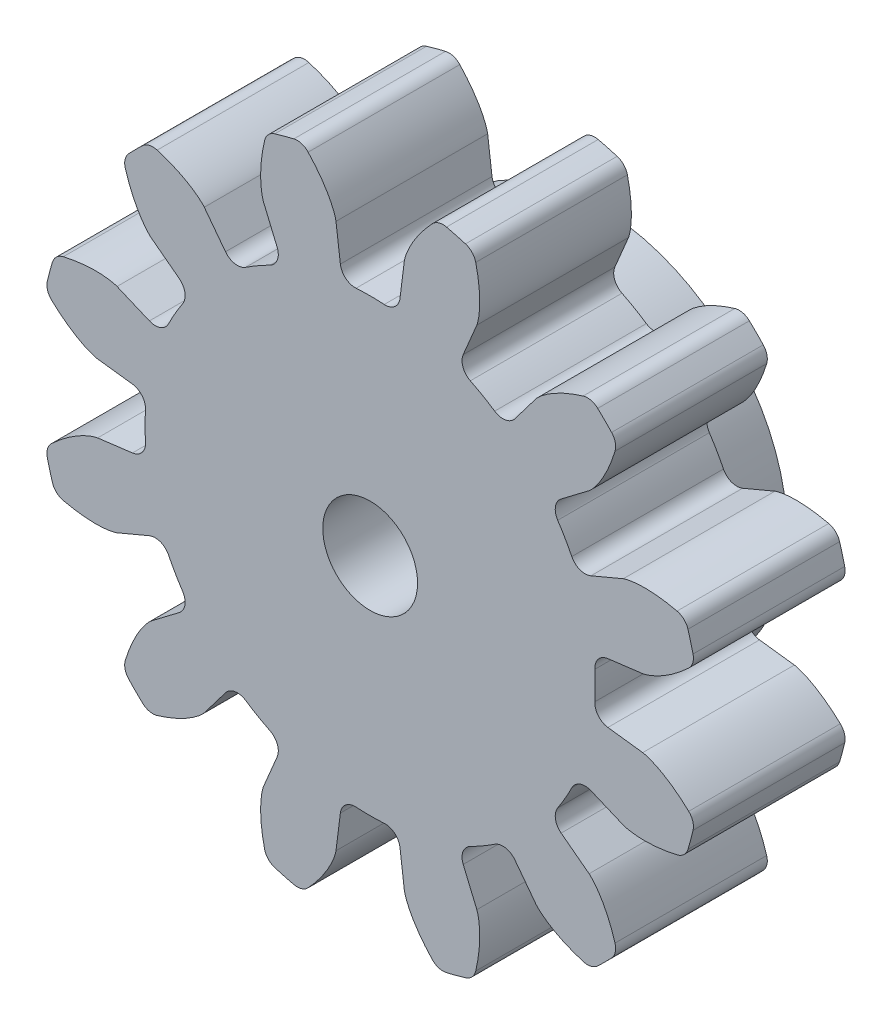
SolidWorks part; units mm, degrees
material "Brass"
ref_plane "Front Plane" through (0, 0, 0) normal (0, 0, 1) x (1, 0, 0)
ref_plane "Top Plane" through (0, 0, 0) normal (0, 1, 0) x (1, 0, 0)
ref_plane "Right Plane" through (0, 0, 0) normal (1, 0, 0) x (0, 0, -1)
sketch "Sketch1" plane through (0, 0, 0) normal (0, 0, 1) x (1, 0, 0)
  circle A0 centre (0, 0) radius 8.75
  dimension "D1" = 17.5
extrude "Boss-Extrude1" add sketch "Sketch1" along normal blind 4
sketch "Sketch2" plane through (0, 0, 4) normal (0, 0, 1) x (1, 0, 0)
  line L0 (7.1881, 0.9014) -> (0, 0) construction
  line L1 (0, 0) -> (7.1881, -0.9014) construction
  line L2 (5.8914, 0.7388) -> (7.1881, 0.9014)
  line L3 (5.8914, -0.7388) -> (7.1881, -0.9014)
  circle A0 centre (0, 0) radius 8.75 construction
  circle A1 centre (0, 0) radius 7.2444 construction
  circle A2 centre (0, 0) radius 7.5 construction
  circle A3 centre (0, 0) radius 5.9375 construction
  arc A4 (8.5637, 1.7962) -> (8.5637, -1.7962) centre (3.6281, 0) cw
  arc A5 (5.8914, -0.7388) -> (5.8914, 0.7388) centre (0, 0) ccw
  spline S0 degree 4 poles (7.1881, 0.9014) (7.1906, 0.9017) (7.1974, 0.9028) (7.2102, 0.9052) (7.231, 0.9098) (7.2574, 0.9165) (7.2912, 0.9262) (7.3308, 0.939) (7.374, 0.9543) (7.4206, 0.9724) (7.4667, 0.9918) (7.5124, 1.0122) (7.5575, 1.0337) (7.6118, 1.061) (7.6764, 1.0954) (7.7509, 1.1381) (7.8343, 1.1894) (7.9181, 1.2449) (7.9996, 1.302) (8.0806, 1.3625) (8.158, 1.4231) (8.2371, 1.489) (8.3094, 1.5512) (8.3888, 1.6241) (8.4524, 1.6838) (8.5346, 1.7659) (8.5825, 1.8154) (8.6381, 1.8744) (8.6624, 1.9012) (8.6774, 1.9177) knots 0 0 0 0 0 0.005377 0.015084 0.028532 0.04661 0.064855 0.092111 0.119476 0.146842 0.174209 0.201575 0.228941 0.256307 0.307035 0.361767 0.4165 0.471232 0.525964 0.580697 0.635429 0.690161 0.744894 0.799626 0.854358 0.909091 0.954545 1 1 1 1 1 construction
  spline S1 degree 4 poles (7.1881, 0.9014) (7.1906, 0.9017) (7.1974, 0.9028) (7.2102, 0.9052) (7.231, 0.9098) (7.2574, 0.9165) (7.2912, 0.9262) (7.3308, 0.939) (7.374, 0.9543) (7.4206, 0.9724) (7.4667, 0.9918) (7.5124, 1.0122) (7.5575, 1.0337) (7.6118, 1.061) (7.6764, 1.0954) (7.7509, 1.1381) (7.8343, 1.1894) (7.9181, 1.2449) (7.9996, 1.302) (8.0806, 1.3625) (8.158, 1.4231) (8.2371, 1.489) (8.3094, 1.5512) (8.3888, 1.6241) (8.4524, 1.6838) (8.5167, 1.7481) (8.5479, 1.7798) (8.5637, 1.7962) knots 0 0 0 0 0 0.005377 0.015084 0.028532 0.04661 0.064855 0.092111 0.119476 0.146842 0.174209 0.201575 0.228941 0.256307 0.307035 0.361767 0.4165 0.471232 0.525964 0.580697 0.635429 0.690161 0.744894 0.799626 0.854358 0.909091 0.909091 0.909091 0.909091 0.909091
  spline S2 degree 4 poles (7.1881, -0.9014) (7.1906, -0.9017) (7.1974, -0.9028) (7.2102, -0.9052) (7.231, -0.9098) (7.2574, -0.9165) (7.2912, -0.9262) (7.3308, -0.939) (7.374, -0.9543) (7.4206, -0.9724) (7.4667, -0.9918) (7.5124, -1.0122) (7.5575, -1.0337) (7.6118, -1.061) (7.6764, -1.0954) (7.7509, -1.1381) (7.8343, -1.1894) (7.9181, -1.2449) (7.9996, -1.302) (8.0806, -1.3625) (8.158, -1.4231) (8.2371, -1.489) (8.3094, -1.5512) (8.3888, -1.6241) (8.4524, -1.6838) (8.5346, -1.7659) (8.5825, -1.8154) (8.6381, -1.8744) (8.6624, -1.9012) (8.6774, -1.9177) knots 0 0 0 0 0 0.005377 0.015084 0.028532 0.04661 0.064855 0.092111 0.119476 0.146842 0.174209 0.201575 0.228941 0.256307 0.307035 0.361767 0.4165 0.471232 0.525964 0.580697 0.635429 0.690161 0.744894 0.799626 0.854358 0.909091 0.954545 1 1 1 1 1 construction
  spline S3 degree 4 poles (7.1881, -0.9014) (7.1906, -0.9017) (7.1974, -0.9028) (7.2102, -0.9052) (7.231, -0.9098) (7.2574, -0.9165) (7.2912, -0.9262) (7.3308, -0.939) (7.374, -0.9543) (7.4206, -0.9724) (7.4667, -0.9918) (7.5124, -1.0122) (7.5575, -1.0337) (7.6118, -1.061) (7.6764, -1.0954) (7.7509, -1.1381) (7.8343, -1.1894) (7.9181, -1.2449) (7.9996, -1.302) (8.0806, -1.3625) (8.158, -1.4231) (8.2371, -1.489) (8.3094, -1.5512) (8.3888, -1.6241) (8.4524, -1.6838) (8.5167, -1.7481) (8.5479, -1.7798) (8.5637, -1.7962) knots 0 0 0 0 0 0.005377 0.015084 0.028532 0.04661 0.064855 0.092111 0.119476 0.146842 0.174209 0.201575 0.228941 0.256307 0.307035 0.361767 0.4165 0.471232 0.525964 0.580697 0.635429 0.690161 0.744894 0.799626 0.854358 0.909091 0.909091 0.909091 0.909091 0.909091
  circle M4 centre (0, 0) radius 8.75
  dimension "D1" = 17.5
  dimension "D2" = 11.875
  dimension "D3" = 15
  dimension "D4" = 14.4889
extrude "Cut-Extrude1" cut sketch "Sketch2" against normal through all contours L3 S3 S1 L2 A5 M4 region at (7.5286, 0, 4)
sketch "Mate" plane through (0, 0, 0) normal (0, 0, 1) x (1, 0, 0)
  circle A0 centre (0, 0) radius 7.5
  circle A1 centre (0, 0) radius 7.5 construction
fillet "Fillet1" radius 0.3934 4 edges at (5.8914, -0.7388, 2) (5.8914, 0.7388, 2) (8.5637, -1.7962, 2) (8.5637, 1.7962, 2)
pattern_circular "CirPattern1" count 12 over 360 about axis through (0, 0, 0) along (0, 0, 1) of "Cut-Extrude1", "Fillet1"
sketch "Sketch4" plane through (0, 0, 0) normal (0, 0, 1) x (1, 0, 0)
  circle A0 centre (0, 0) radius 5
  dimension "D1" = 10
extrude "Boss-Extrude2" add sketch "Sketch4" against normal blind 2
sketch "Sketch3" plane through (0, 0, 0) normal (0, 0, 1) x (1, 0, 0)
  circle A0 centre (0, 0) radius 2.9
  dimension "D1" = 5.8
extrude "Cut-Extrude2" cut sketch "Sketch3" along normal blind 2 and the other way blind 2
sketch "Sketch5" plane through (0, 0, 0) normal (0, 0, 1) x (1, 0, 0)
  circle A0 centre (0, 0) radius 1.25
  dimension "D1" = 2.5
extrude "Cut-Extrude3" cut sketch "Sketch5" along normal through all
equation "\"DiametralPitch\"= 0.8"
equation "\"NumTeeth\" = 12"
equation "\"Addendum\"= 1 / \"DiametralPitch\""
equation "\"Dedendum\"= 1.25 / \"DiametralPitch\""
equation "\"WorkingDepth\"= 2 / \"DiametralPitch\""
equation "\"WholeDepth\"= 2.25 / \"DiametralPitch\""
equation "\"Clearance\"= 0.25 / \"DiametralPitch\""
equation "\"ToothThickness\"= 1.5708 / \"DiametralPitch\""
equation "\"CircularPitch\"= pi / \"DiametralPitch\""
equation "\"PitchCircle\"= \"NumTeeth\" / \"DiametralPitch\""
equation "\"OutsideDiameter\"= ( \"NumTeeth\" + 2 ) / \"DiametralPitch\""
equation "\"AddendumCircle\"= \"PitchCircle\" + ( 2 * \"Addendum\" )"
equation "\"DedendumCircle\"= \"PitchCircle\" - ( 2 * \"Dedendum\" )"
equation "\"PitchAngle\"= 360deg / \"NumTeeth\""
equation "\"PressureAngle\"= 15deg"
equation "\"Width\" = 4mm"
equation "\"Fillet\"= \"Clearance\" * cos ( \"PressureAngle\" ) * tan ( ( 90 + \"PressureAngle\" ) / 2 )"
equation "\"BaseCircle\"= \"PitchCircle\" * cos ( \"PressureAngle\" )"
equation "\"Alpha\"= sqr ( \"PitchCircle\" ^ 2 - \"BaseCircle\" ^ 2 ) / \"BaseCircle\" * 180 / PI - \"PressureAngle\""
equation "\"Beta\"= ( \"PitchAngle\" / 4 - \"Alpha\" )"
equation "\"Phi\"= sqr ( ( \"AddendumCircle\" / 2 ) ^ 2 - ( \"BaseCircle\" / 2 ) ^ 2 ) / ( \"BaseCircle\" / 2 )"
equation "\"D1@Sketch1\"=\"OutsideDiameter\""
equation "\"D1@Boss-Extrude1\"=\"Width\""
equation "\"D1@Sketch2\"=\"OutsideDiameter\""
equation "\"D2@Sketch2\"=\"DedendumCircle\""
equation "\"D3@Sketch2\"=\"PitchCircle\""
equation "\"D4@Sketch2\"=\"BaseCircle\""
equation "\"D1@Fillet1\"=\"Fillet\""
equation "\"D1@CirPattern1\"=\"NumTeeth\""
